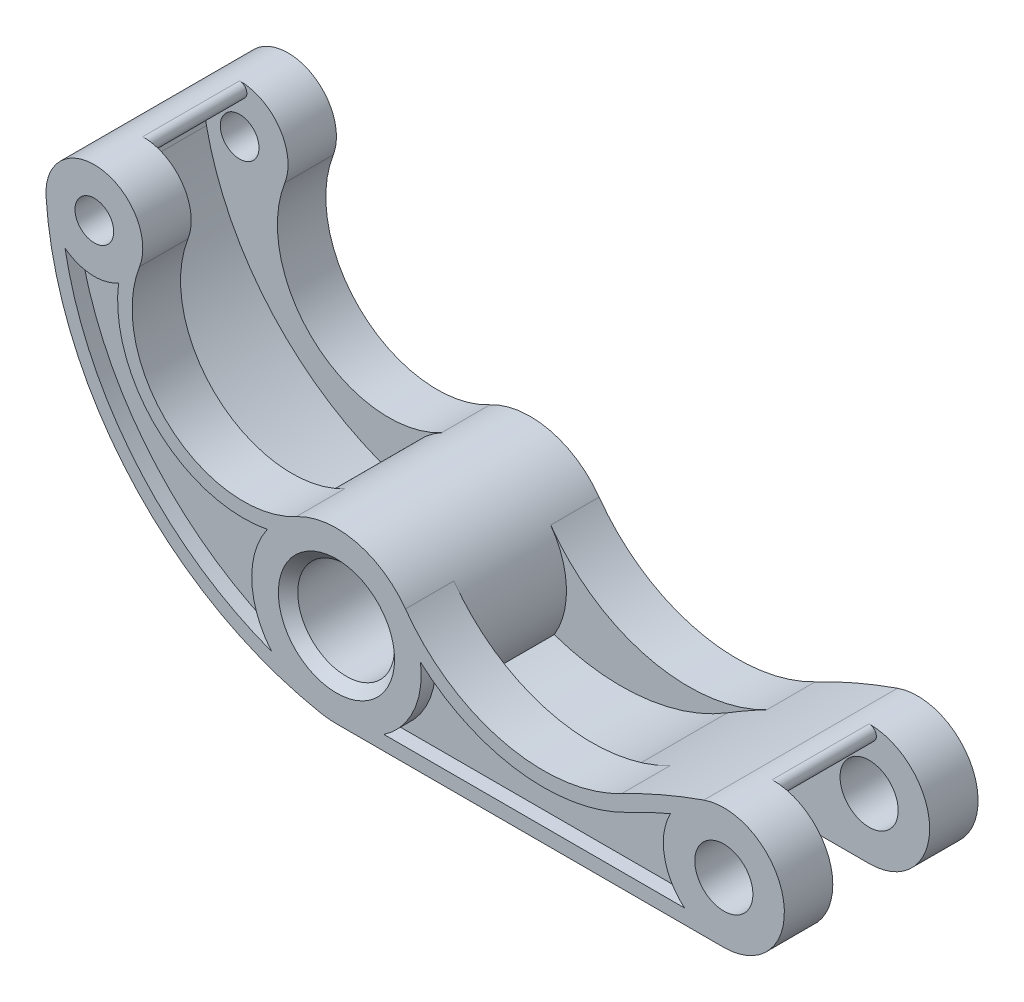
SolidWorks part; units mm, degrees
ref_plane "前视基准面" through (0, 0, 0) normal (0, 0, 1) x (1, 0, 0)
ref_plane "上视基准面" through (0, 0, 0) normal (0, 1, 0) x (1, 0, 0)
ref_plane "右视基准面" through (0, 0, 0) normal (1, 0, 0) x (0, 0, -1)
other "Configuration Table"
sketch "草图1" plane through (0, 0, 0) normal (0, 0, 1) x (1, 0, 0)
  line L0 (0, -17.5) -> (80, -17.5)
  circle A0 centre (-50, 47.5) radius 10
  circle A1 centre (0, 0) radius 17.5
  circle A2 centre (80, -5) radius 12.5
  circle A3 centre (-50, 47.5) radius 4
  circle A4 centre (0, 0) radius 10
  circle A5 centre (80, -5) radius 6
  arc A6 (-59.977, 46.8224) -> (-3.2874, -17.1885) centre (9.8621, 51.5654) ccw
  arc A7 (-40.6656, 43.9126) -> (-8.2948, 15.4093) centre (-19.1966, 35.6615) ccw
  arc A8 (14.2439, 10.1667) -> (58.8803, -0.5519) centre (42.7317, 30.5) ccw
  arc A9 (58.8803, -0.5519) -> (75.8659, 6.7966) centre (118.8607, -115.8878) cw
  point P13 (0, -17.5)
  point P24 (-40.9371, 43.2735)
  point P25 (0, 0)
  dimension "D1" = 20
  dimension "D2" = 8
  dimension "D3" = 35
  dimension "D4" = 20
  dimension "D5" = 25
  dimension "D6" = 12
  dimension "D7" = 70
  dimension "D10" = 23
  dimension "D12" = 35
  dimension "D13" = 130
  dimension "D14" = 48
  dimension "D8" = 65
  dimension "D9" = 50
  dimension "D11" = 80
extrude "凸台-拉伸1" add sketch "草图1" along normal mid plane 40 contours A1 A4 region at (-1.6044, -16.9292, 0)
extrude "凸台-拉伸3" add sketch "草图1<4>" along normal blind 10 from offset 10 contours A9 A8 A1 L0 A2 | A7 A0 A6 A1 region at (41.4922, -9.46, 0) region at (-35.7399, 12.9874, 0)
sketch "草图1<4>" plane through (0, 0, 0) normal (0, 0, 1) x (1, 0, 0) same geometry as "草图1"
extrude "凸台-拉伸6" add sketch "草图1<5>" along normal blind 10 from offset 10 contours A0 A3 | A2 A5 region at (68.0257, -7.0375, 0) region at (-50.3294, 57.2116, 0)
sketch "草图1<5>" plane through (0, 0, 0) normal (0, 0, 1) x (1, 0, 0) same geometry as "草图1"
sketch "草图3" plane through (0, 0, 20) normal (0, 0, 1) x (1, 0, 0)
  arc A0 (-1.1748, -2.9905) -> (52.3251, -7.7119) centre (28.7495, 30.6181) ccw
  arc A1 (76.8581, 3.9654) -> (52.3251, -7.7119) centre (118.8607, -115.8878) ccw
  arc A2 (80, 4.5) -> (76.8581, 3.9654) centre (80, -5) ccw
  arc A3 (75.8659, 6.7966) -> (50.7534, -5.1566) centre (118.8607, -115.8878) ccw
  arc A4 (80, 7.5) -> (75.8659, 6.7966) centre (80, -5) ccw
  arc A5 (-50, 57.5) -> (-59.7858, 45.4412) centre (-50, 47.5) ccw
  arc A6 (-59.7858, 45.4412) -> (-1.1748, -2.9905) centre (-0.0926, 57.9999) ccw
  arc A7 (-2.0535, -2.187) -> (52.3251, -7.7119) centre (28.7495, 30.6181) ccw construction
  circle A8 centre (80, -5) radius 6 construction
  arc A9 (80, 4.5) -> (80, 7.5) centre (80, 6) ccw
  arc A10 (-50, 54.5) -> (-56.85, 46.0588) centre (-50, 47.5) ccw
  arc A11 (-56.85, 46.0588) -> (0, 0) centre (-0.0926, 57.9999) ccw
  arc A12 (80, -14.5) -> (76.8581, 3.9654) centre (80, -5) ccw construction
  arc A13 (75.8659, 6.7966) -> (58.8803, -0.5519) centre (118.8607, -115.8878) ccw construction
  arc A15 (0, 0) -> (50.7534, -5.1566) centre (28.7495, 30.6181) ccw
  arc A16 (-59.7858, 45.4412) -> (0.0048, -3) centre (-0.0926, 57.9999) ccw construction
  arc A17 (-50, 54.5) -> (-50, 57.5) centre (-50, 56) ccw
  arc A18 (-40.7328, 43.7426) -> (-59.7858, 45.4412) centre (-50, 47.5) ccw construction
  arc A19 (-43.5129, 44.8698) -> (-56.85, 46.0588) centre (-50, 47.5) ccw construction
  circle A23 centre (0, 0) radius 10 construction
  circle A24 centre (-50, 47.5) radius 4 construction
  arc A25 (-40.6656, 43.9126) -> (-59.977, 46.8224) centre (-50, 47.5) ccw construction
  arc A26 (-9.9641, 0.8462) -> (-9.7479, -2.2311) centre (0, 0) ccw
  arc A27 (5.8429, -8.1155) -> (8.0531, -5.9286) centre (0, 0) ccw
  arc A28 (80, -17.5) -> (75.8659, 6.7966) centre (80, -5) ccw construction
  arc A29 (80, -17.5) -> (75.8659, 6.7966) centre (80, -5) ccw construction
  point P13 (0, 0)
  arc M7 (75.8659, 6.7966) -> (58.8803, -0.5519) centre (118.8607, -115.8878) ccw
  dimension "D1" = 61
  dimension "D3" = 45
  dimension "D5" = 3
  dimension "D6" = 3
  dimension "D2" = 3
  dimension "D4" = 3
extrude "凸台-拉伸5" add sketch "草图3" against normal blind 10 from offset 10 contours A10 A17 A5 A6 A11 | A2 A3 A15 A0 A1 M7 region at (7.5874, -7.6683, 20) region at (-41.6311, 14.4002, 20) offset against normal yes
sketch "草图4" plane through (0, 0, 20) normal (0, 0, 1) x (1, 0, 0)
  line L9 (0, -14.5) -> (80, -14.5)
  line L10 (9.798, -14.5) -> (71.876, -14.5)
  arc A74 (-14.268, 10.1329) -> (-13.3865, -11.2717) centre (0, 0) ccw
  arc A76 (68.9846, 0.9085) -> (71.876, -14.5) centre (80, -5) ccw
  arc A77 (80, -17.5) -> (75.8659, 6.7966) centre (80, -5) ccw construction
  arc A78 (-56.0494, 39.5373) -> (-45.0017, 38.8387) centre (-50, 47.5) ccw
  arc A79 (-40.6656, 43.9126) -> (-59.977, 46.8224) centre (-50, 47.5) ccw construction
  arc A80 (9.798, -14.5) -> (17.3598, 2.2111) centre (0, 0) ccw
  circle A81 centre (0, 0) radius 10 construction
  arc A82 (11.8021, 8.4238) -> (-6.8729, 12.7677) centre (0, 0) ccw
  arc A83 (-43.4659, 44.9888) -> (-6.8729, 12.7677) centre (-19.1966, 35.6615) ccw
  arc A84 (-43.4659, 44.9888) -> (-56.9839, 47.0257) centre (-50, 47.5) ccw
  arc A85 (-56.9839, 47.0257) -> (-2.7238, -14.2419) centre (9.8621, 51.5654) ccw
  arc A86 (-2.7238, -14.2419) -> (0, -14.5) centre (0, 0) ccw
  arc A87 (80, -14.5) -> (76.8581, 3.9654) centre (80, -5) ccw
  arc A88 (76.8581, 3.9654) -> (60.2645, -3.2135) centre (118.8607, -115.8878) ccw
  arc A89 (11.8021, 8.4238) -> (60.2645, -3.2135) centre (42.7317, 30.5) ccw
  arc A91 (-45.0017, 38.8387) -> (-14.268, 10.1329) centre (-19.1966, 35.6615) ccw
  arc A93 (-56.0494, 39.5373) -> (-13.3865, -11.2717) centre (9.8621, 51.5654) ccw
  arc A96 (68.9846, 0.9085) -> (60.2645, -3.2135) centre (118.8607, -115.8878) ccw
  arc A97 (17.3598, 2.2111) -> (60.2645, -3.2135) centre (42.7317, 30.5) ccw
  dimension "D1" = 3
  dimension "D2" = 7.5
extrude "切除-拉伸2" cut sketch "草图4" against normal blind 3
chamfer "倒角2" distance 2 angle 45 1 edges at (10, 0, 20)
mirror "镜向6" about plane through (0, 0, 0) normal (0, 0, 1) of "凸台-拉伸3", "凸台-拉伸6", "凸台-拉伸5", "切除-拉伸2"
